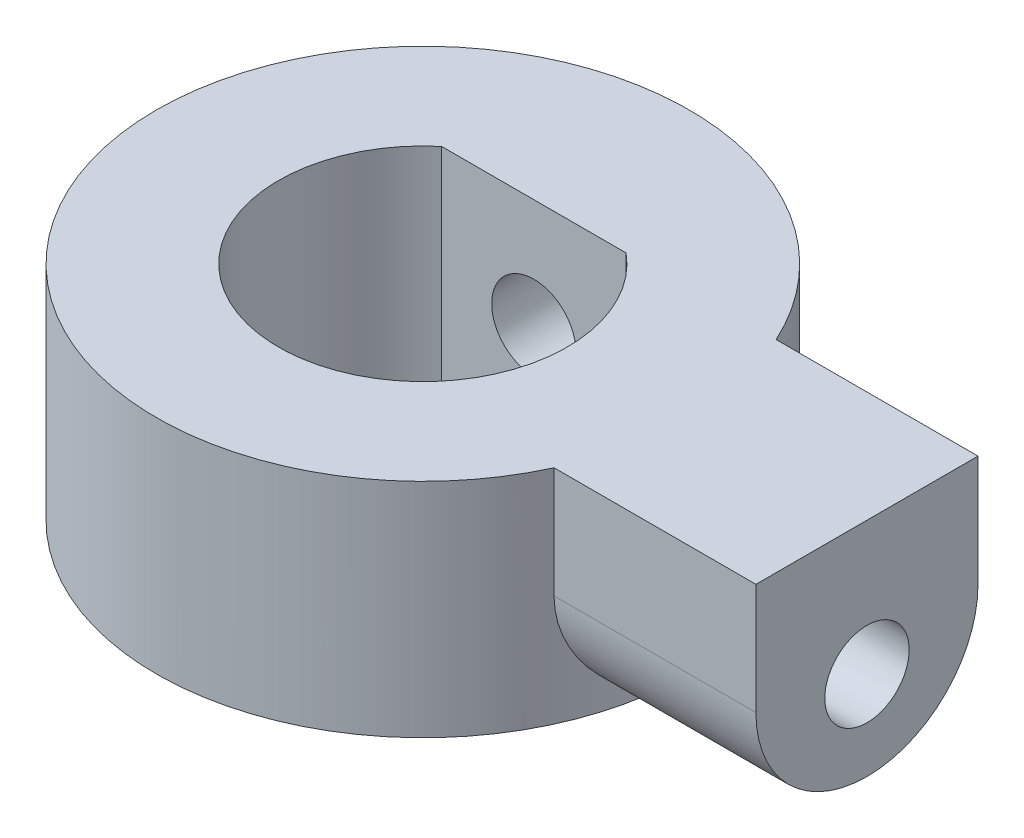
SolidWorks part; units mm, degrees
ref_plane "Plan de face" through (0, 0, 0) normal (0, 0, 1) x (1, 0, 0)
ref_plane "Plan de dessus" through (0, 0, 0) normal (0, 1, 0) x (1, 0, 0)
ref_plane "Plan de droite" through (0, 0, 0) normal (1, 0, 0) x (0, 0, -1)
sketch "Esquisse1" plane through (0, 0, 0) normal (0, 1, 0) x (1, 0, 0)
  line L0 (-2.0767, 2.5) -> (2.0767, 2.5)
  arc A0 (-2.0767, 2.5) -> (2.0767, 2.5) centre (0, 0) ccw
  circle A1 centre (0, 0) radius 6
  dimension "D1" = 6.5
  dimension "D3" = 12
  dimension "D2" = 5.75
extrude "Boss.-Extru.1" add sketch "Esquisse1" along normal blind 5
sketch "Esquisse3" plane through (0, 0, 0) normal (1, 0, 0) x (0, 0, -1)
  line L0 (6, 5) -> (-6, 5) construction
  line L6 (-6, 0) -> (6, 0) construction
  line L7 (-2.5, 2.5) -> (-2.5, 5)
  line L8 (-2.5, 5) -> (2.5, 5)
  line L9 (2.5, 5) -> (-3.25, 5) construction
  line L10 (2.5, 5) -> (2.5, 2.5)
  arc A2 (-2.5, 2.5) -> (2.5, 2.5) centre (0, 2.5) ccw
extrude "Boss.-Extru.2" add sketch "Esquisse3" against normal up to surface (4.5456 mm away) from offset 10 up to face at (0, 5, 6)
sketch "Esquisse4" plane through (10, 0, 0) normal (1, 0, 0) x (0, 0, -1)
  line L2 (-6, 0) -> (6, 0) construction
  circle A0 centre (0, 2) radius 0.95
  dimension "D1" = 1.9
  dimension "D2" = 2
extrude "Enlèv. mat.-Extru.1" cut sketch "Esquisse4" against normal blind 2
sketch "Esquisse5" plane through (0, 0, 0) normal (0, 0, 1) x (1, 0, 0)
  line L0 (2.0767, 5) -> (-2.0767, 5) construction
  line L3 (0, 5) -> (0, 0) construction
  circle A0 centre (0, 2.5) radius 0.95
  point P2 (0, 2.5)
  dimension "D1" = 1.9
extrude "Enlèv. mat.-Extru.2" cut sketch "Esquisse5" against normal blind 8
